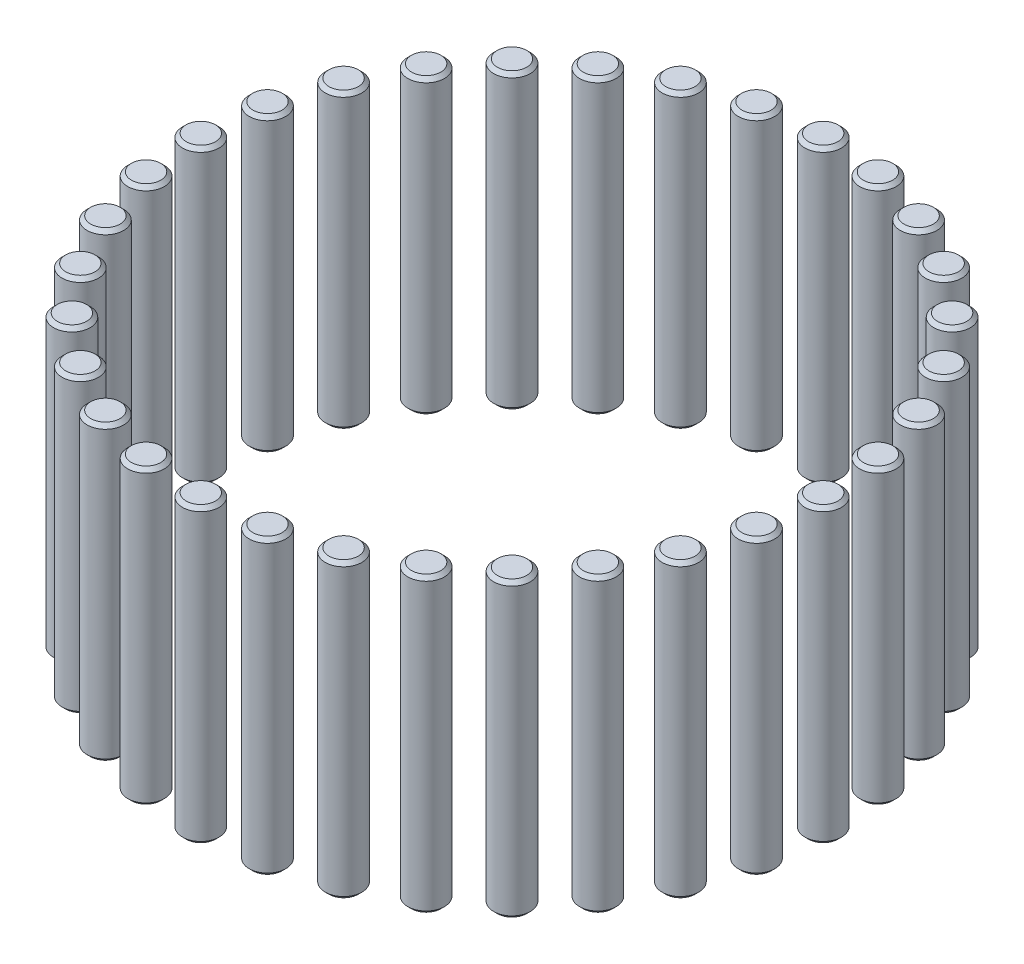
SolidWorks part; units mm, degrees
ref_plane "Front Plane" through (0, 0, 0) normal (0, 0, 1) x (1, 0, 0)
ref_plane "Top Plane" through (0, 0, 0) normal (0, 1, 0) x (1, 0, 0)
ref_plane "Right Plane" through (0, 0, 0) normal (1, 0, 0) x (0, 0, -1)
sketch "Sketch1" plane through (0, 0, 0) normal (0, 0, 1) x (1, 0, 0)
  line L1 (0.5, 8) -> (0, 8)
  line L2 (0.5, 8) -> (0.5, 0)
  line L3 (0.5, 0) -> (0, 0)
  line L4 (0, 8) -> (0, 0)
  line L5 (0.5, 8) -> (0, 0) construction
  line L6 (0.5, 0) -> (0, 8) construction
  point P0 (0.25, 4)
  dimension "D1" = 0.5
  dimension "D2" = 8
revolve "Revolve1" add sketch "Sketch1" angle 360 about L4
ref_axis "Axis1" through (0, 0, 0) along (0, 1, 0)
chamfer "Chamfer1" distance 0.1 angle 45 2 edges at (-0.5, 0, 0) (-0.5, 8, 0)
sketch "Sketch2" plane through (0, 0, 0) normal (0, 1, 0) x (1, 0, 0)
  circle A1 centre (0, -8.5) radius 8 construction
  circle A2 centre (0, 0) radius 0.5 construction
  dimension "D1" = 16
ref_axis "Axis2" through (0, -14.8198, 8.5) along (0, 1, 0)
pattern_circular "CirPattern1" count 32 over 360 about axis through (0, -14.8198, 8.5) along (0, 1, 0) reverse direction yes of bodies 101
